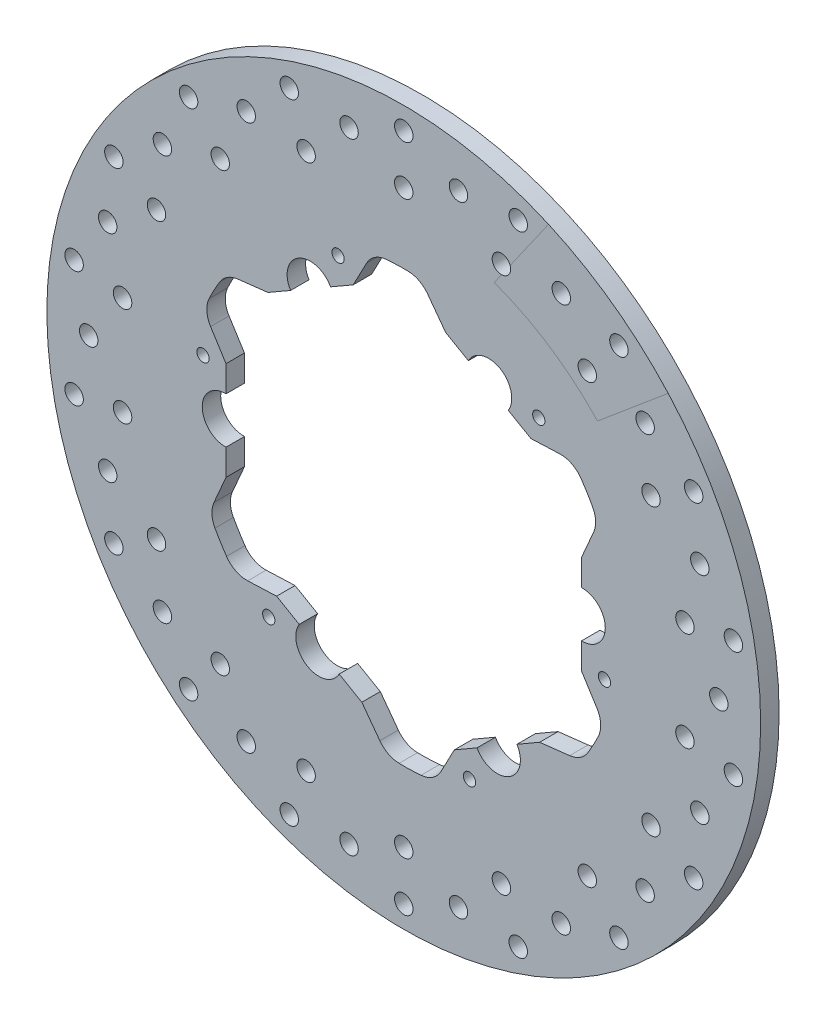
SolidWorks part; units mm, degrees
material "Gray Cast Iron"
ref_plane "Front Plane" through (0, 0, 0) normal (0, 0, 1) x (1, 0, 0)
ref_plane "Top Plane" through (0, 0, 0) normal (0, 1, 0) x (1, 0, 0)
ref_plane "Right Plane" through (0, 0, 0) normal (1, 0, 0) x (0, 0, -1)
sketch "Sketch1" plane through (0, 0, 0) normal (0, 0, 1) x (1, 0, 0)
  line L0 (-55.5625, 0) -> (-55.5625, -25.0191) construction
  line L1 (-45.8597, 11.4094) -> (-45.8597, 4.6599)
  line L2 (-45.8597, 11.4094) -> (-51.6236, 20.5474)
  line L3 (-45.8597, -13.9906) -> (-50.1583, -23.9026)
  line L4 (-45.8597, -7.2411) -> (-45.8597, -13.9906)
  line L5 (-13.049, 45.4204) -> (-8.0172, 54.981)
  line L6 (-13.049, 45.4204) -> (-18.8943, 42.0456)
  line L7 (-29.2008, 36.0951) -> (-35.0461, 32.7204)
  line L8 (-35.0461, 32.7204) -> (-45.7794, 31.4871)
  line L9 (32.8107, 34.011) -> (43.6064, 34.4336)
  line L10 (32.8107, 34.011) -> (26.9654, 37.3857)
  line L11 (16.6589, 43.3362) -> (10.8136, 46.711)
  line L12 (10.8136, 46.711) -> (4.3789, 55.3897)
  line L13 (45.8597, -11.4094) -> (51.6236, -20.5474)
  line L14 (45.8597, -11.4094) -> (45.8597, -4.6599)
  line L15 (45.8597, 7.2411) -> (45.8597, 13.9906)
  line L16 (45.8597, 13.9906) -> (50.1583, 23.9026)
  line L17 (13.049, -45.4204) -> (8.0172, -54.981)
  line L18 (13.049, -45.4204) -> (18.8943, -42.0456)
  line L19 (29.2008, -36.0951) -> (35.0461, -32.7204)
  line L20 (35.0461, -32.7204) -> (45.7794, -31.4871)
  line L21 (-32.8107, -34.011) -> (-43.6064, -34.4336)
  line L22 (-32.8107, -34.011) -> (-26.9654, -37.3857)
  line L23 (-16.6589, -43.3362) -> (-10.8136, -46.711)
  line L24 (-10.8136, -46.711) -> (-4.3789, -55.3897)
  circle A0 centre (0, 0) radius 92.075
  arc A1 (-45.7794, 31.4871) -> (-51.6236, 20.5474) centre (0, 0) ccw
  arc A3 (-45.8597, 4.6599) -> (-45.8597, -7.2411) centre (-46.0375, -1.2906) ccw
  arc A4 (-18.8943, 42.0456) -> (-29.2008, 36.0951) centre (-24.1364, 39.2243) ccw
  arc A5 (26.9654, 37.3857) -> (16.6589, 43.3362) centre (21.9011, 40.5149) ccw
  arc A6 (45.8597, -4.6599) -> (45.8597, 7.2411) centre (46.0375, 1.2906) ccw
  arc A7 (18.8943, -42.0456) -> (29.2008, -36.0951) centre (24.1364, -39.2243) ccw
  arc A8 (-26.9654, -37.3857) -> (-16.6589, -43.3362) centre (-21.9011, -40.5149) ccw
  arc A9 (4.3789, 55.3897) -> (-8.0172, 54.981) centre (0, 0) ccw
  arc A10 (50.1583, 23.9026) -> (43.6064, 34.4336) centre (0, 0) ccw
  arc A11 (45.7794, -31.4871) -> (51.6236, -20.5474) centre (0, 0) ccw
  arc A12 (-4.3789, -55.3897) -> (8.0172, -54.981) centre (0, 0) ccw
  arc A13 (-55.5625, 0) -> (-43.6064, -34.4336) centre (0, 0) ccw
  point P50 (0, 0)
  dimension "D1" = 184.15
  dimension "D2" = 111.125
  dimension "D3" = 11.9062
  dimension "D4" = 9.525
  dimension "D5" = 0.1778
  dimension "D6" = 25.4
  dimension "D7" = 44.45
  dimension "D9" = 47.2577
  dimension "D8" = 6
extrude "Boss-Extrude1" add sketch "Sketch1" along normal blind 4.7625 contours A0 A1 region at (-89.4707, 0, 0)
fillet "Fillet1" radius 6.35 12 edges at (8.0172, -54.981, 2.3813) (45.7794, -31.4871, 2.3813) (-4.3789, -55.3897, 2.3813) (-43.6064, -34.4336, 2.3813) (51.6236, -20.5474, 2.3813) (50.1583, 23.9026, 2.3813) (43.6064, 34.4336, 2.3813) (4.3789, 55.3897, 2.3813) (-50.1583, -23.9026, 2.3813) (-51.6236, 20.5474, 2.3813) (-8.0172, 54.981, 2.3813) (-45.7794, 31.4871, 2.3813)
sketch "Sketch4" plane through (0, 0, 4.7625) normal (0, 0, 1) x (1, 0, 0)
  circle A0 centre (-16.953, 50.0113) radius 1.5875
  arc A1 (-18.8943, 42.0456) -> (-29.2008, 36.0951) centre (-24.1364, 39.2243) ccw construction
  circle A3 centre (34.8346, 39.6874) radius 1.5875
  circle A4 centre (51.7876, -10.3239) radius 1.5875
  circle A5 centre (16.953, -50.0113) radius 1.5875
  circle A6 centre (-34.8346, -39.6874) radius 1.5875
  circle A7 centre (-51.7876, 10.3239) radius 1.5875
  point P6 (-27.113, 44.3799)
  point P23 (0, 0)
  dimension "D1" = 52.8066
  dimension "D2" = 3.175
  dimension "D3" = 10.16
  dimension "D4" = 6
extrude "Cut-Extrude1" cut sketch "Sketch4" against normal through all
sketch "Sketch5" plane through (0, 0, 4.7625) normal (0, 0, 1) x (1, 0, 0)
  line L0 (0, 120.6115) -> (0, 84.6416) construction
  line L1 (-74.0774, 0) -> (83.9652, 0) construction
  line L2 (0, 0) -> (20.7529, 117.6956) construction
  circle A0 centre (0, 0) radius 68.58 construction
  circle A4 centre (0, 86.36) radius 2.3812
  circle A5 centre (0, 73.66) radius 2.3812
  circle A6 centre (14.1141, 80.0452) radius 2.3812
  dimension "D1" = 137.16
  dimension "D2" = 4.7625
  dimension "D3" = 12.7
  dimension "D4" = 86.36
  dimension "D5" = 10
  dimension "D6" = 81.28
extrude "Cut-Extrude2" cut sketch "Sketch5" against normal through all
sketch "Sketch6" plane through (0, 0, 4.7625) normal (0, 0, 1) x (1, 0, 0)
  line L0 (0, 0) -> (0, 110.5188) construction
  line L1 (0, 0) -> (38.9978, 107.1456) construction
  line L4 (23.3472, 64.1458) -> (37.3582, 84.1556)
  line L5 (49.9701, 46.5054) -> (68.2294, 61.8268)
  arc A2 (68.2294, 61.8268) -> (37.3582, 84.1556) centre (0, 0) ccw
  arc A3 (49.9701, 46.5054) -> (23.3472, 64.1458) centre (0, 0) ccw
  dimension "D2" = 15
  dimension "D3" = 184.15
  dimension "D6" = 136.525
  dimension "D1" = 20
  dimension "D4" = 15
  dimension "D5" = 38.1
split line "Split Line1"
pattern_circular "FrontPaternCopy" count 18 over 360 about axis through (0, 0, 4.7625) along (0, 0, 1) of "Cut-Extrude2"
sketch "Sketch7" plane through (0, 0, 4.7625) normal (0, 0, 1) x (1, 0, 0)
  line L0 (0, 0) -> (-24.1364, 39.2243) construction
equation "\"holenumber\"=18"
equation "\"D1@FrontPaternCopy\"=\"holenumber\""
